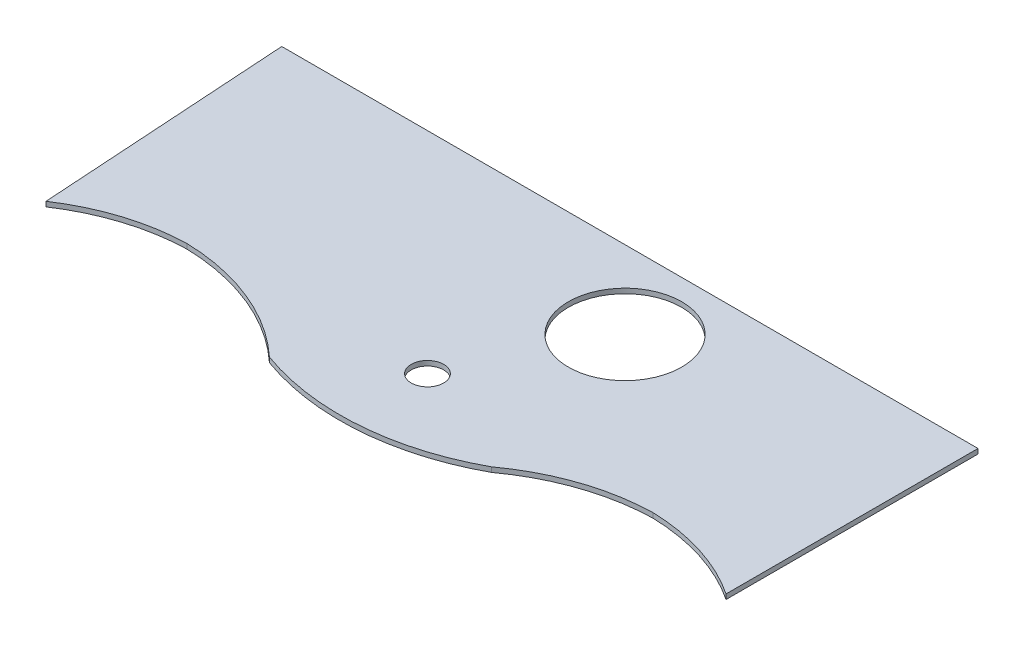
SolidWorks part; units mm, degrees
ref_plane "Front Plane" through (0, 0, 0) normal (0, 0, 1) x (1, 0, 0)
ref_plane "Top Plane" through (0, 0, 0) normal (0, 1, 0) x (1, 0, 0)
ref_plane "Right Plane" through (0, 0, 0) normal (1, 0, 0) x (0, 0, -1)
ref_plane "Plane1" through (0, 22.5, 0) normal (0, 1, 0) x (1, 0, 0)
ref_plane "Plane2" through (0, 24, 0) normal (0, 1, 0) x (1, 0, 0)
sketch "Sketch2" plane through (0, 22.5, 0) normal (0, 1, 0) x (1, 0, 0)
  line L0 (0, -100) -> (0, 70) construction
  line L5 (105, 50) -> (105, -27.799)
  line L6 (-110, 50) -> (-105, -27.799)
  line L7 (71.9147, -28) -> (71.9147, -17.3273) construction
  line L8 (-110, 50) -> (105, 50)
  arc A0 (-105, -27.799) -> (-71.9147, -17.3273) centre (-70.2175, -80.192) cw
  arc A1 (-71.9147, -17.3273) -> (-105, -27.799) centre (-70.2175, -80.192) ccw construction
  arc A2 (-71.9147, -17.3273) -> (-28.8274, -34.9717) centre (-73.6989, -83.1159) cw
  arc A3 (-34.8399, -30) -> (-71.9147, -17.3273) centre (-73.6989, -83.1159) ccw construction
  arc A4 (-28.8274, -34.9717) -> (34.8399, -30) centre (-2.5, 38.0274) ccw
  arc A5 (-39.8399, -30) -> (34.8399, -30) centre (-2.5, 38.0274) ccw construction
  arc A6 (34.8399, -30) -> (71.9147, -17.3273) centre (73.6989, -83.1159) cw
  arc A7 (71.9147, -17.3273) -> (34.8399, -30) centre (73.6989, -83.1159) ccw construction
  arc A8 (71.9147, -17.3273) -> (105, -27.799) centre (70.2175, -80.192) cw
  arc A9 (105, -27.799) -> (71.9147, -17.3273) centre (70.2175, -80.192) ccw construction
  circle A12 centre (20, 26) radius 17.5
  circle A13 centre (20, 26) radius 17.5 construction
  circle A14 centre (0, -15) radius 5
  circle A15 centre (0, -15) radius 5 construction
  point P0 (0, 10.0408)
extrude "Boss-Extrude2" add sketch "Sketch2" along normal up to surface (1.5 mm away) up to plane "Plane2"
